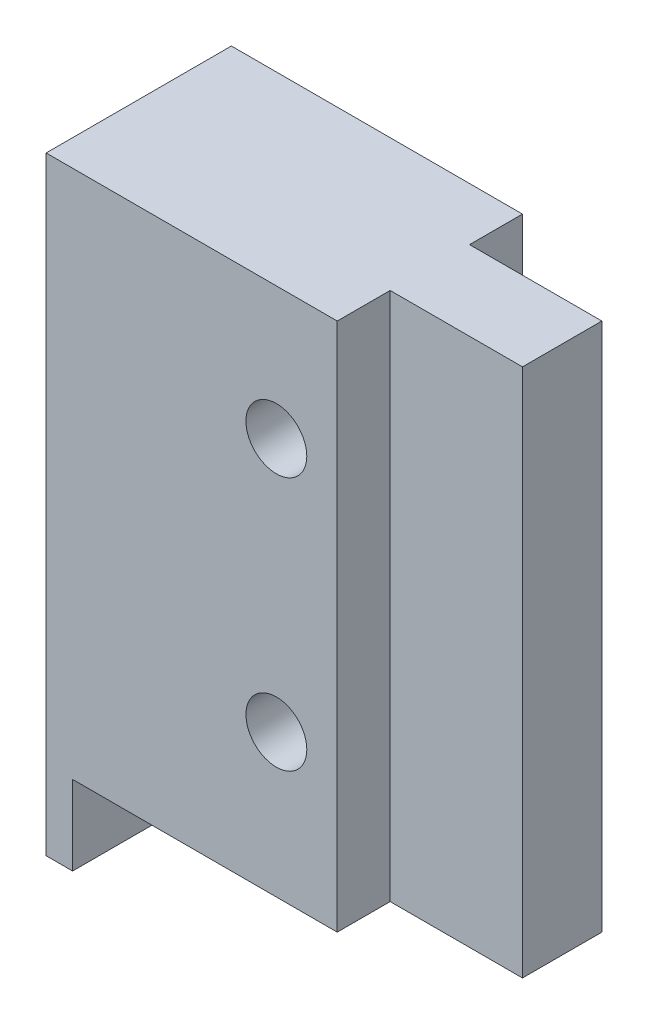
SolidWorks part; units mm, degrees
ref_plane "Front Plane" through (0, 0, 0) normal (0, 0, 1) x (1, 0, 0)
ref_plane "Top Plane" through (0, 0, 0) normal (0, 1, 0) x (1, 0, 0)
ref_plane "Right Plane" through (0, 0, 0) normal (1, 0, 0) x (0, 0, -1)
sketch "Sketch1" plane through (0, 0, 0) normal (0, 0, 1) x (1, 0, 0)
  line L0 (1, 3) -> (16, 3)
  line L1 (0, 0) -> (1, 0)
  line L2 (0, 0) -> (0, 23)
  line L3 (0, 23) -> (16, 23)
  line L4 (16, 3) -> (16, 23)
  line L5 (1, 3) -> (1, 0)
  line L6 (16, 19.7) -> (7, 19.7) construction
  line L7 (7, 19.7) -> (7, 16.3) construction
  line L8 (7, 16.3) -> (16, 16.3) construction
  line L9 (-2.0395, 13.2) -> (18.293, 13.2) construction
  line L10 (7, 10.1) -> (16, 10.1) construction
  line L11 (7, 6.7) -> (7, 10.1) construction
  line L12 (16, 6.7) -> (7, 6.7) construction
  line L13 (11, 23) -> (11, 3)
  circle A0 centre (8.7, 18) radius 1.7 construction
  circle A1 centre (8.7, 18) radius 1.15
  circle A2 centre (8.7, 8.4) radius 1.7 construction
  circle A3 centre (8.7, 8.4) radius 1.15
  dimension "D8" = 2.3
  dimension "D1" = 16
  dimension "D2" = 23
  dimension "D3" = 3
  dimension "D4" = 15
  dimension "D5" = 3.3
  dimension "D6" = 3.4
  dimension "D7" = 9
  dimension "D9" = 13
  dimension "D10" = 5
extrude "Boss-Extrude1" add sketch "Sketch1" along normal blind 3.5 and the other way blind 3.5 contours L13 L3 L2 L1 L5 L0 A1 A3 region at (5.3063, 12.8316, 0)
extrude "Boss-Extrude2" add sketch "Sketch1<3>" along normal blind 1.5 and the other way blind 1.5 contours L3 L13 L0 L4 region at (13.5, 13, 0)
sketch "Sketch1<3>" plane through (0, 0, 0) normal (0, 0, 1) x (1, 0, 0) same geometry as "Sketch1"
